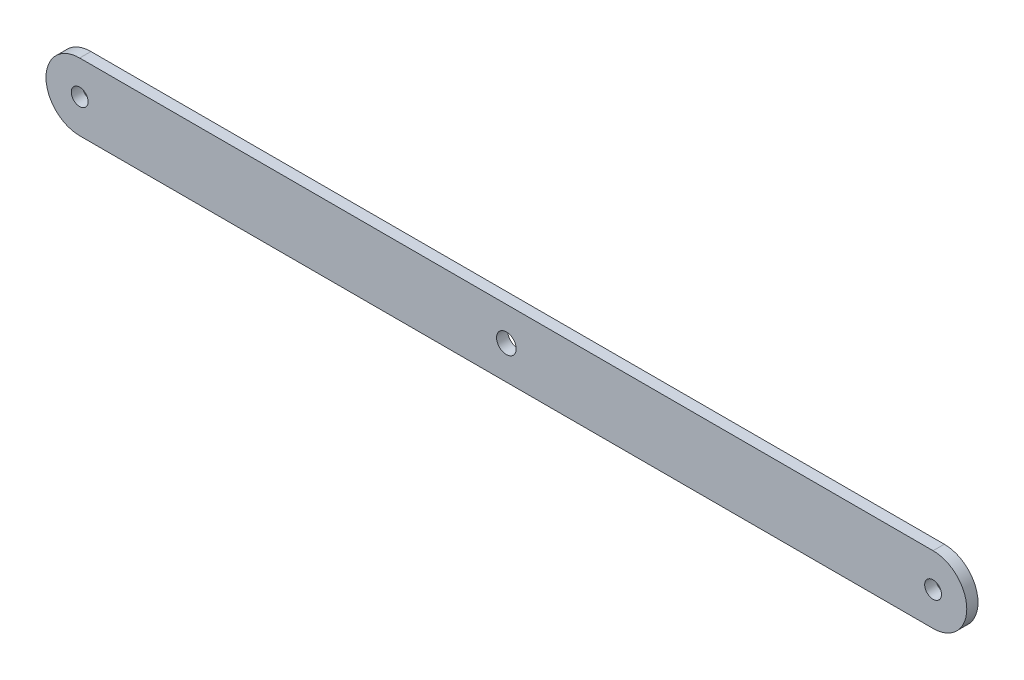
SolidWorks part; units mm, degrees
ref_plane "Front Plane" through (0, 0, 0) normal (0, 0, 1) x (1, 0, 0)
ref_plane "Top Plane" through (0, 0, 0) normal (0, 1, 0) x (1, 0, 0)
ref_plane "Right Plane" through (0, 0, 0) normal (1, 0, 0) x (0, 0, -1)
ref_axis "X" through (-88.99, 0, 0) along (1, 0, 0)
ref_axis "Y" through (0, 55, 0) along (0, -1, 0)
ref_axis "Z" through (0, 0, -88.99) along (0, 0, 1)
sketch "Sketch1" plane through (0, 0, 0) normal (0, 0, 1) x (1, 0, 0)
  line L0 (-76, 0) -> (76, 0) construction
  line L1 (-76, 6) -> (76, 6)
  line L2 (-76, -6) -> (76, -6)
  line L4 (-15, 6) -> (15, 6) construction
  arc A0 (-76, 6) -> (-76, -6) centre (-76, 0) ccw
  arc A1 (76, -6) -> (76, 6) centre (76, 0) ccw
  circle A2 centre (-76, 0) radius 1.5
  circle A3 centre (0, 0) radius 1.75
  circle A4 centre (76, 0) radius 1.5
  circle A5 centre (-76, 0) radius 1.5 construction
  circle A6 centre (0, 0) radius 1.75 construction
  point P2 (0, 0)
extrude "Boss-Extrude1" add sketch "Sketch1" along normal blind 2
